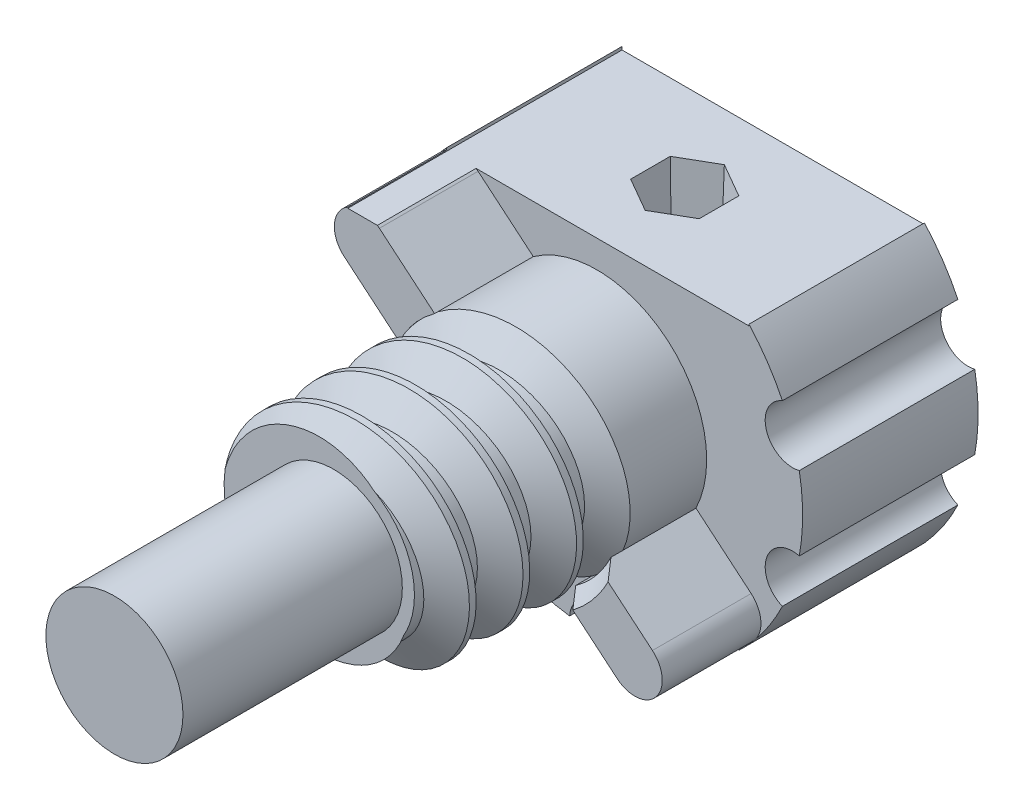
SolidWorks part; units mm, degrees
ref_plane "Front" through (0, 0, 0) normal (0, 0, 1) x (1, 0, 0)
ref_plane "Top" through (0, 0, 0) normal (0, 1, 0) x (1, 0, 0)
ref_plane "Right" through (0, 0, 0) normal (1, 0, 0) x (0, 0, -1)
sketch "Sketch1" plane through (0, 0, 0) normal (0, 0, 1) x (1, 0, 0)
  line L0 (-1.5351, 0.94) -> (1.5351, 0.94)
  line L1 (0, 0.94) -> (0, -1.8) construction
  arc A0 (-1.5351, 0.94) -> (1.5351, 0.94) centre (0, 0) ccw
  circle A1 centre (0, 0) radius 7.5
  dimension "D1" = 2.74
  dimension "D2" = 1.8
extrude "Boss-Extrude1" add sketch "Sketch1" along normal blind 7
sketch "Sketch2" plane through (0, 0, 7) normal (0, 0, 1) x (1, 0, 0)
  circle A0 centre (0, 0) radius 4
extrude "Boss-Extrude2" add sketch "Sketch2" along normal blind 9
sketch "Sketch3" plane through (0, 0, 7) normal (0, 0, 1) x (1, 0, 0)
  line L0 (-7.5, 0) -> (7.5, 0) construction
  line L5 (5.7453, -4.8209) -> (-5.7453, 4.8209) construction
  line L6 (5.6221, -3.4121) -> (-4.3365, 4.9442)
  line L8 (4.3365, -4.9442) -> (-5.6221, 3.4121)
  circle A3 centre (0, 0) radius 7.5 construction
  arc A4 (4.3365, -4.9442) -> (5.6221, -3.4121) centre (4.9793, -4.1781) ccw
  arc A5 (-4.3365, 4.9442) -> (-5.6221, 3.4121) centre (-4.9793, 4.1781) ccw
  dimension "D6" = 2
  dimension "D7" = 2
  dimension "D5" = 40
extrude "Boss-Extrude3" add sketch "Sketch3" along normal blind 3
thread "Thread1" pitch 1.9538 start angle 0, offset 1.75, length 8, pitch 1.9538, diameter 8
ref_plane "Plane1" through (-4, 0, 17.75) normal (0, -1, 0) x (-1, 0, 0)
sketch "Thread Profile1" plane through (-4, 0, 17.75) normal (0, -1, 0) x (-1, 0, 0)
  line L0 (0, 0) -> (0, 1.9538) construction
  line L11 (0, 0) -> (0, 1.7096)
  line L12 (0, 1.7096) -> (-1.0576, 1.099)
  line L13 (-1.0576, 1.099) -> (-1.0576, 0.6106)
  line L15 (-1.0576, 0.6106) -> (0, 0)
  line L17 (-1.0576, 0.8548) -> (0, 0.8548) construction
  point P2 (0, 0)
  dimension "Pitch" = 1.9538
  dimension "Profile_Angle" = 60
  dimension "Profile_Land" = 0.4885
  dimension "Profile_Height" = 1.0576
sketch "Sketch5" plane through (0, 0, 7) normal (0, 0, 1) x (1, 0, 0)
  line L3 (-4.3365, 4.9442) -> (-2.3241, 3.2556)
  line L4 (3.6097, -1.7235) -> (5.6221, -3.4121)
  line L5 (-4.3365, 4.9442) -> (-2.3241, 3.2556)
  line L6 (3.6097, -1.7235) -> (5.6221, -3.4121)
  line L7 (-3.6097, 1.7235) -> (-5.6221, 3.4121)
  line L8 (4.3365, -4.9442) -> (2.3241, -3.2556)
  line L9 (-3.6097, 1.7235) -> (-5.6221, 3.4121)
  line L10 (4.3365, -4.9442) -> (2.3241, -3.2556)
  arc A0 (-3.6097, 1.7235) -> (2.3241, -3.2556) centre (0, 0) ccw
  arc A1 (3.6097, -1.7235) -> (-2.3241, 3.2556) centre (0, 0) ccw
  arc A4 (5.7453, -4.8209) -> (-5.7453, 4.8209) centre (0, 0) ccw
  arc A5 (-4.3365, 4.9442) -> (-5.7453, 4.8209) centre (-4.9793, 4.1781) ccw
  arc A6 (3.6097, -1.7235) -> (-2.3241, 3.2556) centre (0, 0) ccw
  arc A7 (5.7453, -4.8209) -> (5.6221, -3.4121) centre (4.9793, -4.1781) ccw
  arc A8 (5.7453, -4.8209) -> (-5.7453, 4.8209) centre (0, 0) ccw
  arc A9 (-4.3365, 4.9442) -> (-5.7453, 4.8209) centre (-4.9793, 4.1781) ccw
  arc A11 (5.7453, -4.8209) -> (5.6221, -3.4121) centre (4.9793, -4.1781) ccw
  arc A12 (-3.6097, 1.7235) -> (2.3241, -3.2556) centre (0, 0) ccw
  arc A13 (-5.7453, 4.8209) -> (-5.6221, 3.4121) centre (-4.9793, 4.1781) ccw
  arc A14 (-5.7453, 4.8209) -> (5.7453, -4.8209) centre (0, 0) ccw
  arc A15 (4.3365, -4.9442) -> (5.7453, -4.8209) centre (4.9793, -4.1781) ccw
  arc A17 (-5.7453, 4.8209) -> (-5.6221, 3.4121) centre (-4.9793, 4.1781) ccw
  arc A18 (-5.7453, 4.8209) -> (5.7453, -4.8209) centre (0, 0) ccw
  arc A19 (4.3365, -4.9442) -> (5.7453, -4.8209) centre (4.9793, -4.1781) ccw
  arc M13 (5.7453, -4.8209) -> (-5.7453, 4.8209) centre (0, 0) ccw
  arc M14 (-5.7453, 4.8209) -> (-4.3365, 4.9442) centre (-4.9793, 4.1781) cw
  line M15 (-4.3365, 4.9442) -> (-2.3241, 3.2556)
  line M17 (3.6097, -1.7235) -> (5.6221, -3.4121)
  arc M18 (5.6221, -3.4121) -> (5.7453, -4.8209) centre (4.9793, -4.1781) cw
  dimension "D1" = 0
  dimension "D2" = 0
extrude "Cut-Extrude1" cut sketch "Sketch5" against normal blind 0.6 contours A1 M17 M18 M13 M14 M15 | A19 L10 A0 L9 A17 A18
sketch "Sketch6" plane through (0, 0, 0) normal (0, 0, -1) x (-1, 0, 0)
  circle A0 centre (0, 7.5) radius 1
  circle A1 centre (0, 0) radius 7.5 construction
  dimension "D1" = 2
extrude "Cut-Extrude2" cut sketch "Sketch6" against normal up to surface (6.4 mm away) up to face at (1.5978, 1.9042, 6.4)
sketch "Sketch11" plane through (0, 0, 7) normal (0, 0, -1) x (-1, 0, 0)
  line L0 (1.5351, 0.94) -> (-1.5351, 0.94)
  arc A0 (-1.5351, 0.94) -> (1.5351, 0.94) centre (0, 0) ccw
  point P6 (0, 0.94)
extrude "Cut-Extrude5" cut sketch "Sketch11" against normal blind 2.5
pattern_circular "CirPattern1" count 10 over 360 about axis through (0, 0, 0) along (0, 0, 1) of "Cut-Extrude2"
ref_plane "Plane2" through (0, 5, 0) normal (0, 1, 0) x (1, 0, 0)
sketch "Sketch8" plane through (0, 5, 0) normal (0, 1, 0) x (1, 0, 0)
  line L1 (5.5416, -13.865) -> (-5.4868, -13.865)
  line L2 (5.5416, -13.865) -> (5.5416, 0)
  line L3 (5.5416, 0) -> (-5.4868, 0)
  line L4 (-5.4868, -13.865) -> (-5.4868, 0)
  line L5 (5.5416, -13.865) -> (-5.4868, 0) construction
  line L6 (5.5416, 0) -> (-5.4868, -13.865) construction
  point P4 (0.0274, -6.9325)
extrude "Cut-Extrude3" cut sketch "Sketch8" along normal through all
sketch "Sketch9" plane through (0, 5, 0) normal (0, 1, 0) x (1, 0, 0)
  line L0 (0, 0) -> (0, -6.4) construction
  line L2 (-2.2913, -6.4) -> (2.2913, -6.4) construction
  line L3 (0, -1.7566) -> (-1.25, -2.4783)
  line L4 (-1.25, -2.4783) -> (-1.25, -3.9217)
  line L5 (-1.25, -3.9217) -> (0, -4.6434)
  line L6 (0, -4.6434) -> (1.25, -3.9217)
  line L7 (1.25, -3.9217) -> (1.25, -2.4783)
  line L8 (1.25, -2.4783) -> (0, -1.7566)
  circle A1 centre (0, -3.2) radius 1.25 construction
  dimension "D1" = 2.5
extrude "Cut-Extrude4" cut sketch "Sketch9" against normal up to surface (4.06 mm away) draft 2
sketch "Sketch10" plane through (0, 0, 16) normal (0, 0, 1) x (1, 0, 0)
  circle A0 centre (0, 0) radius 2.5
  dimension "D1" = 5
extrude "Boss-Extrude6" add sketch "Sketch10" along normal blind 8
chamfer "Chamfer1" distance 0.78 angle 60 2 edges at (0, 0.94, 9.5) (0, -1.8, 9.5)
chamfer "Chamfer2" distance 0.5 angle 45 1 edges
